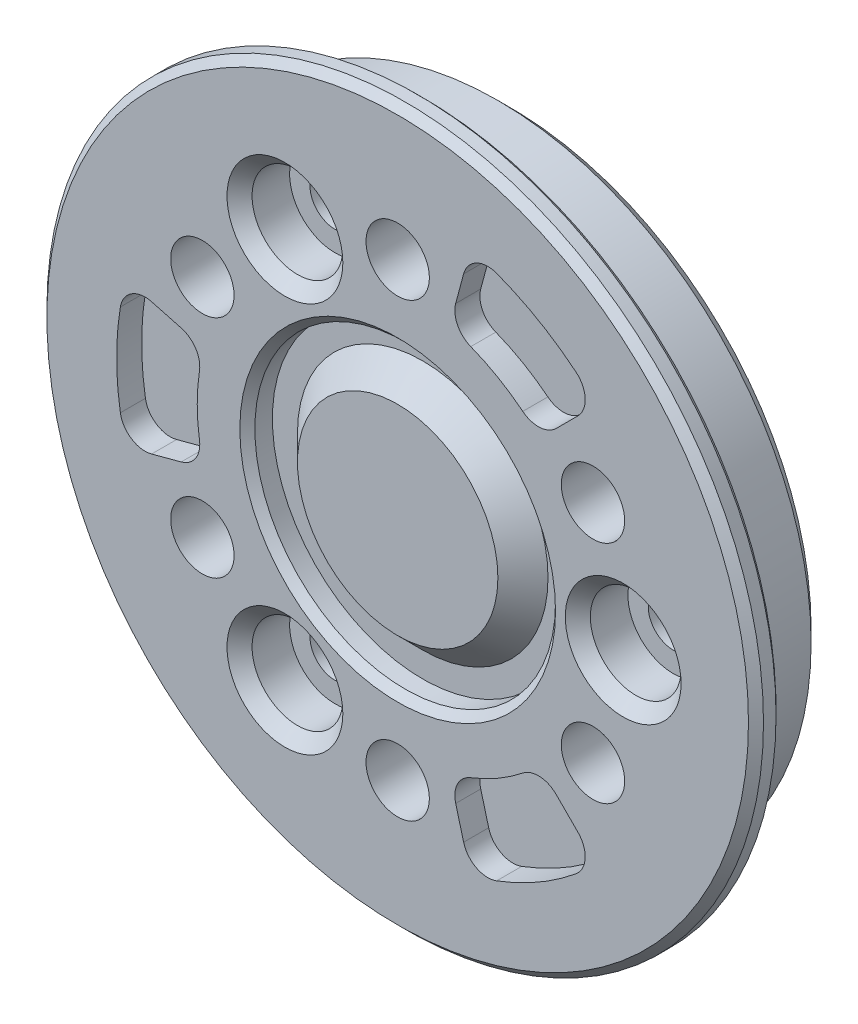
SolidWorks part; units mm, degrees
ref_plane "Front Plane" through (0, 0, 0) normal (0, 0, 1) x (1, 0, 0)
ref_plane "Top Plane" through (0, 0, 0) normal (0, 1, 0) x (1, 0, 0)
ref_plane "Right Plane" through (0, 0, 0) normal (1, 0, 0) x (0, 0, -1)
sketch "Sketch1" plane through (0, 0, 0) normal (0, 1, 0) x (1, 0, 0)
  line L0 (14.3, -9.2) -> (0, -9.2)
  line L1 (0, -9.2) -> (0, -10.2)
  line L2 (0, -10.2) -> (14.3, -10.2)
  line L3 (14.3, -10.2) -> (14.3, -9.2)
  line L4 (0, -9.2) -> (0, -10.2) construction
revolve "Revolve1" add sketch "Sketch1" angle 360 about L4 reverse direction yes
sketch "Sketch2" plane through (0, 0, 9.2) normal (0, 0, -1) x (-1, 0, 0)
  circle A0 centre (0, 0) radius 12.5
extrude "Boss-Extrude1" add sketch "Sketch2" along normal blind 3.5
hole_wizard "Ø7.0 (7) Diameter Hole1" positions "Sketch4" profile "Sketch3" hole size "Ø7.0" standard "ANSI Metric"
sketch "Sketch4" plane through (0, 0, 5.7) normal (0, 0, 1) x (1, 0, 0)
  point P0 (0, 0)
sketch "Sketch3" plane through (0, 0, 5.7) normal (1, 0, 0) x (0, 1, 0)
  line L0 (0, 0) -> (0, 3.3)
  line L1 (0, 3.3) -> (3.5, 3.3)
  line L2 (3.5, 3.3) -> (3.5, 0)
  line L5 (3.5, 0) -> (0, 0)
  line L10 (0, 3.3) -> (-3.5, 3.3) construction
  line L11 (0, -6.35) -> (0, 107.95) construction
  dimension "Hole Dia." = 7
  dimension "Hole Depth" = 3.3
  dimension "Drill Angle" = 180
sketch "Sketch17" plane through (0, 0, 9) normal (0, 0, -1) x (-1, 0, 0)
  circle A0 centre (0, 0) radius 3.25
  circle A1 centre (0, 0) radius 3.5 construction
  circle A2 centre (0, 0) radius 3.5
  dimension "D1" = 6.5
extrude "Boss-Extrude3" add sketch "Sketch17" along normal blind 0.5
ref_plane "Plane1" through (0, 0, 9.2) normal (0, 0, -1) x (-1, 0, 0)
sketch "Sketch18" plane through (0, 0, 10.2) normal (0, 0, 1) x (1, 0, 0)
  circle A0 centre (0, 0) radius 6
  dimension "D1" = 12
extrude "Cut-Extrude4" cut sketch "Sketch18" against normal blind 1
sketch "Sketch19" plane through (0, 0, 9.2) normal (0, 0, 1) x (1, 0, 0)
  circle A0 centre (0, 0) radius 4
  dimension "D1" = 8
extrude "Boss-Extrude4" add sketch "Sketch19" along normal blind 1
sketch "Sketch6" plane through (0, 0, 10.2) normal (0, 0, 1) x (1, 0, 0)
  line L0 (2.9033, 10.8352) -> (2.0706, 7.7274)
  line L1 (5.6569, 5.6569) -> (7.9319, 7.9319)
  arc A0 (7.9319, 7.9319) -> (2.9033, 10.8352) centre (0, 0) ccw
  arc A1 (2.0706, 7.7274) -> (5.6569, 5.6569) centre (0, 0) cw
extrude "Cut-Extrude1" cut sketch "Sketch6" against normal blind 1
sketch "Sketch7" plane through (0, 0, 10.2) normal (0, 0, 1) x (1, 0, 0)
  line L0 (7.9319, -7.9319) -> (5.6569, -5.6569)
  line L1 (2.0706, -7.7274) -> (2.9033, -10.8352)
  arc A0 (2.9033, -10.8352) -> (7.9319, -7.9319) centre (0, 0) ccw
  arc A1 (5.6569, -5.6569) -> (2.0706, -7.7274) centre (0, 0) cw
extrude "Cut-Extrude2" cut sketch "Sketch7" against normal blind 1
sketch "Sketch8" plane through (0, 0, 10.2) normal (0, 0, 1) x (1, 0, 0)
  line L0 (-10.8352, -2.9033) -> (-7.7274, -2.0706)
  line L1 (-7.7274, 2.0706) -> (-10.8352, 2.9033)
  arc A0 (-10.8352, 2.9033) -> (-10.8352, -2.9033) centre (0, 0) ccw
  arc A1 (-7.7274, -2.0706) -> (-7.7274, 2.0706) centre (0, 0) cw
extrude "Cut-Extrude3" cut sketch "Sketch8" against normal blind 1
hole_wizard "Ø2.0 (2) Diameter Hole1" positions "Sketch10" profile "Sketch9" hole size "Ø2.0" standard "ANSI Metric"
sketch "Sketch10" plane through (0, 0, 5.7) normal (0, 0, -1) x (-1, 0, 0)
  point P0 (-4.5, 7.7942)
  point P1 (9, 0)
  point P2 (-4.5, -7.7942)
sketch "Sketch9" plane through (4.5, 7.7942, 5.7) normal (1, 0, 0) x (0, 1, 0)
  line L0 (0, 0) -> (0, 2.3)
  line L1 (0, 2.3) -> (1, 2.3)
  line L2 (1, 2.3) -> (1, 0)
  line L5 (1, 0) -> (0, 0)
  line L10 (0, 2.3) -> (-1, 2.3) construction
  line L11 (0, -6.35) -> (0, 107.95) construction
  dimension "Hole Dia." = 2
  dimension "Hole Depth" = 2.3
  dimension "Drill Angle" = 180
hole_wizard "CBORE for M1.6 SHCS1" positions "Sketch12" profile "Sketch11" counterbore size "M1.6" standard "ANSI Metric"
sketch "Sketch12" plane through (0, 0, 10.2) normal (0, 0, 1) x (1, 0, 0)
  point P0 (-4.5, 7.7942)
  point P1 (-4.5, -7.7942)
  point P2 (9, 0)
sketch "Sketch11" plane through (-4.5, 7.7942, 10.2) normal (1, 0, 0) x (0, -1, 0)
  line L0 (0, 0) -> (0, 4.5)
  line L1 (0, 4.5) -> (1, 4.5)
  line L3 (1, 4.5) -> (1, 2)
  line L4 (1, 2) -> (1.8115, 2)
  line L5 (1.8115, 2) -> (1.8115, 0)
  line L7 (1.8115, 0) -> (0, 0)
  line L11 (0, -6.35) -> (0, 107.95) construction
  dimension "Thru Hole Dia." = 2
  dimension "Thru Hole Depth" = 4.5
  dimension "C'Bore Dia." = 3.623
  dimension "C'Bore Depth" = 2
hole_wizard "M2 Clearance Hole1" positions "Sketch16" profile "Sketch15" hole size "M2" standard "ANSI Metric"
sketch "Sketch16" plane through (0, 0, 10.2) normal (0, 0, 1) x (1, 0, 0)
  point P0 (7.7942, -4.5)
  point P1 (-7.7942, -4.5)
  point P2 (7.7942, 4.5)
  point P3 (0, -9)
  point P4 (-7.7942, 4.5)
  point P5 (0, 9)
sketch "Sketch15" plane through (7.7942, -4.5, 10.2) normal (1, 0, 0) x (0, -1, 0)
  line L0 (0, 0) -> (0, 4)
  line L1 (0, 4) -> (1.2645, 4)
  line L2 (1.2645, 4) -> (1.2645, 0)
  line L5 (1.2645, 0) -> (0, 0)
  line L10 (0, 4) -> (-1.2645, 4) construction
  line L11 (0, -6.35) -> (0, 107.95) construction
  dimension "Hole Dia." = 2.529
  dimension "Hole Depth" = 4
  dimension "Drill Angle" = 180
chamfer "Chamfer1" distance 0.5 angle 45 4 edges at (-2.6885, 7.7942, 10.2) (-2.6885, -7.7942, 10.2) (10.8115, 0, 10.2) (-12.5, 0, 5.7)
chamfer "Chamfer2" distance 0.3 angle 45 2 edges at (14.3, 0, 10.2) (6, 0, 10.2)
chamfer "Chamfer3" distance 0.2 angle 45 1 edges at (14.3, 0, 9.2)
chamfer "Chamfer4" distance 1 angle 45 1 edges at (4, 0, 9.2)
fillet "Fillet1" radius 1 12 edges at (7.9319, -7.9319, 9.7) (-10.8352, -2.9033, 9.7) (-7.7274, 2.0706, 9.7) (7.9319, 7.9319, 9.7) (5.6569, -5.6569, 9.7) (2.0706, 7.7274, 9.7) (-10.8352, 2.9033, 9.7) (2.9033, 10.8352, 9.7) (-7.7274, -2.0706, 9.7) (2.9033, -10.8352, 9.7) (2.0706, -7.7274, 9.7) (5.6569, 5.6569, 9.7) tangent propagation no
